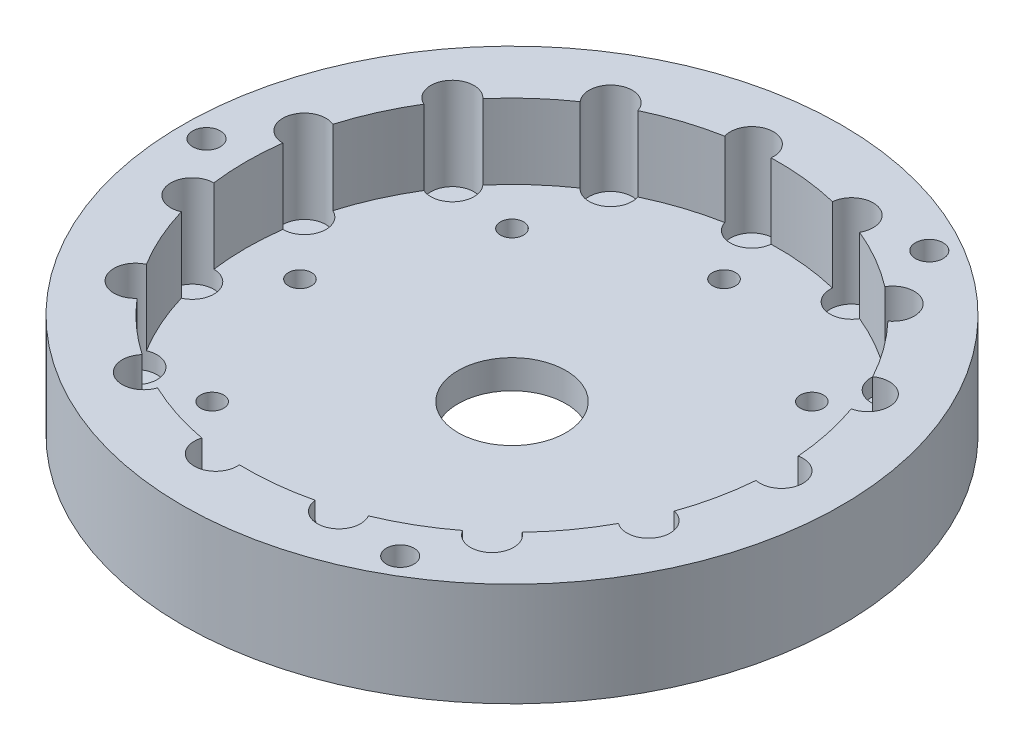
SolidWorks part; units mm, degrees
ref_plane "Front Plane" through (0, 0, 0) normal (0, 0, 1) x (1, 0, 0)
ref_plane "Top Plane" through (0, 0, 0) normal (0, 1, 0) x (1, 0, 0)
ref_plane "Right Plane" through (0, 0, 0) normal (1, 0, 0) x (0, 0, -1)
sketch "Sketch1" plane through (0, 0, 0) normal (0, 1, 0) x (1, 0, 0)
  line L0 (0, 0) -> (-42.5, 0) construction
  circle A0 centre (0, 0) radius 7.5
  circle A1 centre (0, 0) radius 45.85
  circle A2 centre (0, 0) radius 37.5 construction
  circle A3 centre (37.5, 0) radius 3
  circle A4 centre (34.258, 15.2526) radius 3
  circle A5 centre (25.0924, 27.8679) radius 3
  circle A6 centre (11.5881, 35.6646) radius 3
  circle A7 centre (-3.9198, 37.2946) radius 3
  circle A8 centre (-18.75, 32.476) radius 3
  circle A9 centre (-30.3381, 22.0419) radius 3
  circle A10 centre (-36.6805, 7.7967) radius 3
  circle A11 centre (-36.6805, -7.7967) radius 3
  circle A12 centre (-30.3381, -22.0419) radius 3
  circle A13 centre (-18.75, -32.476) radius 3
  circle A14 centre (-3.9198, -37.2946) radius 3
  circle A15 centre (11.5881, -35.6646) radius 3
  circle A16 centre (25.0924, -27.8679) radius 3
  circle A17 centre (34.258, -15.2526) radius 3
  circle A19 centre (0, 0) radius 29.5 construction
  circle A20 centre (29.5, 0) radius 1.607
  circle A21 centre (20.8597, -20.8597) radius 1.607
  circle A22 centre (0, -29.5) radius 1.607
  circle A23 centre (-20.8597, -20.8597) radius 1.607
  circle A24 centre (-29.5, 0) radius 1.607
  circle A25 centre (-20.8597, 20.8597) radius 1.607
  circle A26 centre (0, 29.5) radius 1.607
  circle A27 centre (20.8597, 20.8597) radius 1.607
  arc A28 (36.8833, 2.9359) -> (34.8888, 12.3197) centre (0, 0) ccw
  arc A29 (34.8888, -12.3197) -> (36.8833, -2.9359) centre (0, 0) ccw
  arc A30 (26.8616, -25.4451) -> (32.5004, -17.6839) centre (0, 0) ccw
  arc A31 (14.1898, -34.1709) -> (22.4979, -29.3742) centre (0, 0) ccw
  arc A32 (-0.9355, -36.9882) -> (8.6053, -35.9854) centre (0, 0) ccw
  arc A33 (-15.8991, -33.4099) -> (-6.7752, -36.3744) centre (0, 0) ccw
  arc A34 (-28.1135, -24.0547) -> (-20.9843, -30.4739) centre (0, 0) ccw
  arc A35 (-35.4669, -10.5403) -> (-31.5649, -19.3043) centre (0, 0) ccw
  arc A36 (-36.6878, 4.7967) -> (-36.6878, -4.7967) centre (0, 0) ccw
  arc A37 (-31.5649, 19.3043) -> (-35.4669, 10.5403) centre (0, 0) ccw
  arc A38 (-20.9843, 30.4739) -> (-28.1135, 24.0547) centre (0, 0) ccw
  arc A39 (-6.7752, 36.3744) -> (-15.8991, 33.4099) centre (0, 0) ccw
  arc A40 (8.6053, 35.9854) -> (-0.9355, 36.9882) centre (0, 0) ccw
  arc A41 (22.4979, 29.3742) -> (14.1898, 34.1709) centre (0, 0) ccw
  arc A42 (32.5004, 17.6839) -> (26.8616, 25.4451) centre (0, 0) ccw
  circle A43 centre (-42.5, 0) radius 1.5635
  circle A44 centre (21.25, 36.8061) radius 1.5635
  circle A45 centre (21.25, -36.8061) radius 1.5635
  point P38 (0, 0)
  point P57 (0, 0)
  point P87 (0, 0)
  point P92 (0, 0)
  dimension "D2" = 15
  dimension "D3" = 75
  dimension "D4" = 91.7
  dimension "D5" = 6
  dimension "D8" = 3.214
  dimension "D9" = 59
  dimension "D6" = 37
  dimension "D12" = 3.127
  dimension "D11" = 42.5
  dimension "D1" = 15
  dimension "D7" = 8
  dimension "D10" = 15
  dimension "D13" = 3
extrude "Boss-Extrude1" add sketch "Sketch1" against normal blind 4 contours A4 A42 A5 A41 A6 A40 A7 A39 A8 A38 A9 A37 A10 A36 A11 A35 A12 A34 A13 A33 A14 A32 A15 A31 A16 A30 A17 A29 A3 A28 A0 A20 A21 A22 A23 A24 A25 A26 A27 | A3 | A17 | A4 | A5 | A6 | A7 | A8 | A9 | A10 | A11 | A12 | A13 | A14 | A15 | A16 | A1 A42 A4 A28 A3 A29 A17 A30 A16 A31 A15 A32 A14 A33 A13 A34 A12 A35 A11 A36 A10 A37 A9 A38 A8 A39 A7 A40 A6 A41 A5 | A22 | A23 | A24 | A25 | A26 | A27 | A20 | A21 region at (-44.5532, 0, 0) region at (37.5, 0, 0) region at (33.4543, 0, 0) region at (34.258, 0, -15.2526) region at (34.258, 0, 15.2526) region at (25.0924, 0, -27.8679) region at (25.0924, 0, 27.8679) region at (11.5881, 0, -35.6646) region at (11.5881, 0, 35.6646) region at (-3.9198, 0, -37.2946) region at (-3.9198, 0, 37.2946) region at (-18.75, 0, -32.476) region at (-18.75, 0, 32.476) region at (-30.3381, 0, -22.0419) region at (-30.3381, 0, 22.0419) region at (-36.6805, 0, -7.7967) region at (-36.6805, 0, 7.7967) region at (29.5, 0, 0) region at (20.8597, 0, 20.8597) region at (0, 0, 29.5) region at (-20.8597, 0, 20.8597) region at (-29.5, 0, 0) region at (-20.8597, 0, -20.8597) region at (0, 0, -29.5) region at (20.8597, 0, -20.8597)
extrude "Cut-Extrude1" cut sketch "Sketch1<6>" against normal blind 2.4105 contours A24 | A25 | A26 | A27 | A20 | A21 | A22 | A23 | A10 | A11 | A9 | A12 | A13 | A14 | A15 | A16 | A17 | A3 | A4 | A5 | A6 | A7 | A8 region at (37.5, 0, 0) region at (34.258, 0, -15.2526) region at (34.258, 0, 15.2526) region at (25.0924, 0, -27.8679) region at (25.0924, 0, 27.8679) region at (11.5881, 0, -35.6646) region at (11.5881, 0, 35.6646) region at (-3.9198, 0, -37.2946) region at (-3.9198, 0, 37.2946) region at (-18.75, 0, -32.476) region at (-18.75, 0, 32.476) region at (-30.3381, 0, -22.0419) region at (-30.3381, 0, 22.0419) region at (-36.6805, 0, -7.7967) region at (-36.6805, 0, 7.7967) region at (29.5, 0, 0) region at (20.8597, 0, 20.8597) region at (0, 0, 29.5) region at (-20.8597, 0, 20.8597) region at (-29.5, 0, 0) region at (-20.8597, 0, -20.8597) region at (0, 0, -29.5) region at (20.8597, 0, -20.8597)
sketch "Sketch1<6>" plane through (0, 0, 0) normal (0, 1, 0) x (1, 0, 0) same geometry as "Sketch1"
extrude "Boss-Extrude2" add sketch "Sketch1<7>" along normal blind 10.4105 contours A1 A42 A4 A28 A3 A29 A17 A30 A16 A31 A15 A32 A14 A33 A13 A34 A12 A35 A11 A36 A10 A37 A9 A38 A8 A39 A7 A40 A6 A41 A5 region at (-44.5532, 0, 0)
sketch "Sketch1<7>" plane through (0, 0, 0) normal (0, 1, 0) x (1, 0, 0) same geometry as "Sketch1"
sketch "Sketch2" plane through (0, 10.4105, 0) normal (0, 1, 0) x (1, 0, 0)
  circle A0 centre (-42.5, 0) radius 1.925
  circle A1 centre (21.25, 36.8061) radius 1.925
  circle A2 centre (21.25, -36.8061) radius 1.925
  point P10 (0, 0)
  dimension "D2" = 3.85
  dimension "D1" = 3
extrude "Cut-Extrude2" cut sketch "Sketch2" against normal blind 4
equation "\"bearing_21_OD\"= 21mm"
equation "\"D2@Sketch1\"=\"bearing_15_OD\"+0mm"
equation "\"pin_cirlce_diameter\"= 75mm"
equation "\"D3@Sketch1\"=\"pin_cirlce_diameter\""
equation "\"pin_diam\"= 6mm"
equation "\"D5@Sketch1\"=\"pin_diam\""
equation "\"gear_thickness\"= 4mm"
equation "\"ball_bearing_diam\"= 3.214mm"
equation "\"bearing_21_outer_clearance\"= 0.127mm'change this"
equation "\"bearing_15_OD\"= 15mm"
equation "\"bearing_15_outer_clearance\"= 0mm'change this"
equation "\"D8@Sketch1\"=\"ball_bearing_diam\""
equation "\"D1@Cut-Extrude1\"=\"ball_bearing_diam\"*0.75"
equation "\"thrust_bearing_thickness\"= 5mm'measure this irl and change"
equation "\"D1@Boss-Extrude2\"=\"ball_bearing_diam\"*0.75mm+2*\"gear_thickness\""
